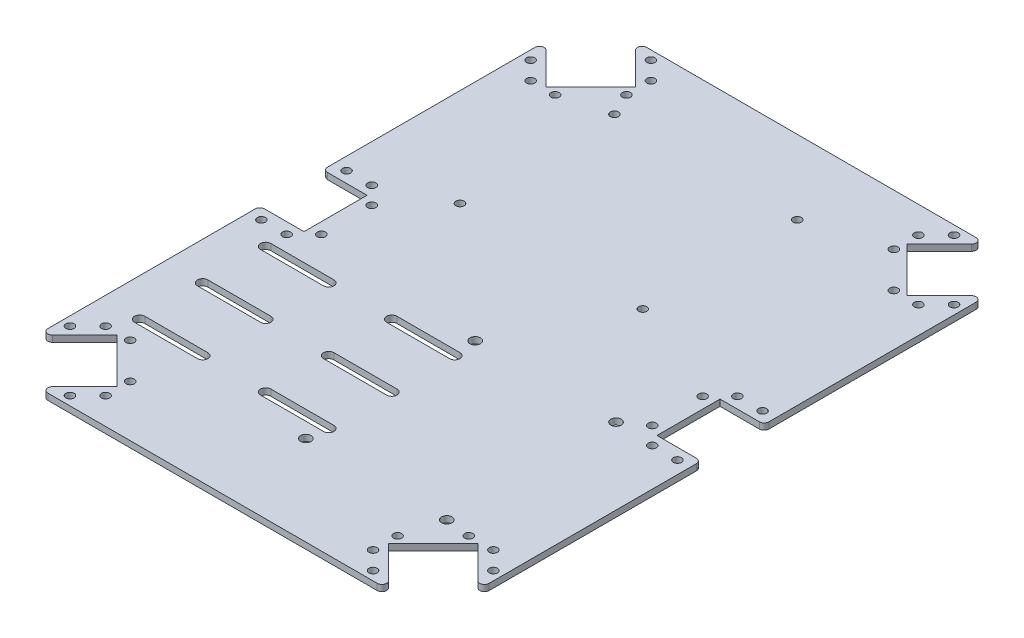
SolidWorks part; units mm, degrees
ref_plane "Front Plane" through (0, 0, 0) normal (0, 0, 1) x (1, 0, 0)
ref_plane "Top Plane" through (0, 0, 0) normal (0, 1, 0) x (1, 0, 0)
ref_plane "Right Plane" through (0, 0, 0) normal (1, 0, 0) x (0, 0, -1)
sketch "Sketch2" plane through (0, 0, 0) normal (0, 1, 0) x (1, 0, 0)
  line L0 (-70, 0) -> (70, 0) construction
  line L1 (-70, 95) -> (70, 95)
  line L2 (-70, 95) -> (-70, -95)
  line L3 (-70, -95) -> (70, -95)
  line L4 (70, 95) -> (70, -95)
  line L5 (70, 95) -> (0, 25) construction
  line L7 (0, 95) -> (0, -95) construction
  line L8 (42.4228, 78.7365) -> (38.5337, 82.6256) construction
  line L9 (38.5337, 82.6256) -> (42.4228, 86.5147) construction
  line L10 (42.4228, 86.5147) -> (48.0797, 92.1716) construction
  line L11 (48.0797, 92.1716) -> (50.9081, 95) construction
  circle A5 centre (42.4228, 78.7365) radius 1.3
  circle A6 centre (42.4228, 86.5147) radius 1.3
  circle A7 centre (48.0797, 92.1716) radius 1.3
  circle A8 centre (66, 13.5) radius 1.3
  circle A9 centre (58, 13.5) radius 1.3
  circle A10 centre (52.5, 8) radius 1.3
  circle A11 centre (52.5, -8) radius 1.3
  circle A12 centre (58, -13.5) radius 1.3
  circle A13 centre (66, -13.5) radius 1.3
  circle A14 centre (67.1716, 73.0797) radius 1.3
  circle A15 centre (61.5147, 67.4228) radius 1.3
  circle A16 centre (53.7365, 67.4228) radius 1.3
  circle A17 centre (67.1716, -73.0797) radius 1.3
  circle A18 centre (61.5147, -67.4228) radius 1.3
  circle A19 centre (53.7365, -67.4228) radius 1.3
  circle A20 centre (48.0797, -92.1716) radius 1.3
  circle A21 centre (42.4228, -86.5147) radius 1.3
  circle A22 centre (42.4228, -78.7365) radius 1.3
  circle A23 centre (-48.0797, 92.1716) radius 1.3
  circle A24 centre (-42.4228, 86.5147) radius 1.3
  circle A25 centre (-42.4228, 78.7365) radius 1.3
  circle A26 centre (-67.1716, 73.0797) radius 1.3
  circle A27 centre (-61.5147, 67.4228) radius 1.3
  circle A28 centre (-53.7365, 67.4228) radius 1.3
  circle A29 centre (-67.1716, -73.0797) radius 1.3
  circle A30 centre (-61.5147, -67.4228) radius 1.3
  circle A31 centre (-53.7365, -67.4228) radius 1.3
  circle A32 centre (-42.4228, -78.7365) radius 1.3
  circle A33 centre (-42.4228, -86.5147) radius 1.3
  circle A34 centre (-48.0797, -92.1716) radius 1.3
  circle A35 centre (-52.5, -8) radius 1.3
  circle A36 centre (-58, -13.5) radius 1.3
  circle A37 centre (-66, -13.5) radius 1.3
  circle A38 centre (-66, 13.5) radius 1.3
  circle A39 centre (-58, 13.5) radius 1.3
  circle A40 centre (-52.5, 8) radius 1.3
  point P0 (0, 0)
  point P27 (0, 0)
  dimension "D6" = 5.5
  dimension "D10" = 8
  dimension "D11" = 5.5
  dimension "D2" = 2.6
  dimension "D3" = 8
  dimension "D4" = 4
  dimension "D5" = 5.5
  dimension "D7" = 45
  dimension "D8" = 140
  dimension "D9" = 190
  dimension "D12" = 5.5
  dimension "D13" = 8
  dimension "D14" = 4
  dimension "D15" = 8
extrude "Boss-Extrude1" add sketch "Sketch2" along normal blind 2
sketch "Sketch3" plane through (0, 2, 0) normal (0, 1, 0) x (1, 0, 0)
  line L0 (0, -95) -> (0, 95) construction
  line L1 (-70, -95) -> (70, -95) construction
  line L2 (70, 95) -> (-70, 95) construction
  line L3 (-70, 0) -> (70, 0) construction
  line L4 (-70, 95) -> (-70, -95) construction
  line L5 (70, -95) -> (70, 95) construction
  line L6 (70, 95) -> (0, 25) construction
  line L7 (70, -10) -> (56, -10)
  line L8 (70, -10) -> (70, 10)
  line L9 (70, 10) -> (56, 10)
  line L10 (56, -10) -> (56, 10)
  line L11 (55.8579, 95) -> (43.1299, 82.2721)
  line L12 (43.1299, 82.2721) -> (57.2721, 68.1299)
  line L13 (57.2721, 68.1299) -> (70, 80.8579)
  line L14 (70, 80.8579) -> (70, 95)
  line L15 (70, 95) -> (55.8579, 95)
  line L16 (70, -80.8579) -> (70, -95)
  line L17 (57.2721, -68.1299) -> (70, -80.8579)
  line L18 (43.1299, -82.2721) -> (57.2721, -68.1299)
  line L19 (55.8579, -95) -> (43.1299, -82.2721)
  line L20 (70, -95) -> (55.8579, -95)
  line L21 (-70, 80.8579) -> (-70, 95)
  line L22 (-57.2721, 68.1299) -> (-70, 80.8579)
  line L23 (-43.1299, 82.2721) -> (-57.2721, 68.1299)
  line L24 (-55.8579, 95) -> (-43.1299, 82.2721)
  line L25 (-70, 95) -> (-55.8579, 95)
  line L26 (-70, 10) -> (-56, 10)
  line L27 (-56, -10) -> (-56, 10)
  line L28 (-70, -10) -> (-56, -10)
  line L29 (-70, -10) -> (-70, 10)
  line L30 (-57.2721, -68.1299) -> (-70, -80.8579)
  line L31 (-43.1299, -82.2721) -> (-57.2721, -68.1299)
  line L32 (-55.8579, -95) -> (-43.1299, -82.2721)
  line L33 (-70, -95) -> (-55.8579, -95)
  line L34 (-70, -80.8579) -> (-70, -95)
  dimension "D1" = 10
  dimension "D2" = 20
  dimension "D3" = 14
  dimension "D4" = 45
  dimension "D5" = 18
  dimension "D6" = 20
  dimension "D7" = 10
extrude "Cut-Extrude1" cut sketch "Sketch3" against normal up to surface (2 mm away) up to face at (0, 0, 0)
fillet "Fillet1" radius 1.5 12 edges at (-70, 1, 10) (-70, 1, -10) (-70, 1, 80.8579) (-55.8579, 1, 95) (55.8579, 1, 95) (70, 1, 80.8579) (70, 1, 10) (70, 1, -10) (70, 1, -80.8579) (55.8579, 1, -95) (-70, 1, -80.8579) (-55.8579, 1, -95)
sketch "Sketch4" plane through (0, 2, 0) normal (0, 1, 0) x (1, 0, 0)
  line L1 (-39, 71.5) -> (19, 71.5) construction
  line L2 (-39, 71.5) -> (-39, 22.5) construction
  line L3 (-39, 22.5) -> (19, 22.5) construction
  line L4 (19, 71.5) -> (19, 22.5) construction
  line L5 (-42.5, 75) -> (42.5, 75) construction
  line L6 (-42.5, 75) -> (-42.5, 19) construction
  line L7 (-42.5, 19) -> (42.5, 19) construction
  line L8 (42.5, 75) -> (42.5, 19) construction
  line L9 (52.2365, 95) -> (-52.2365, 95) construction
  line L10 (-70, 77.2365) -> (-70, 11.5) construction
  circle A0 centre (-39, 71.5) radius 1.3
  circle A1 centre (19, 71.5) radius 1.3
  circle A2 centre (19, 22.5) radius 1.3
  circle A3 centre (-39, 22.5) radius 1.3
  dimension "D1" = 2.6
  dimension "D2" = 58
  dimension "D3" = 85
  dimension "D4" = 56
  dimension "D5" = 49
  dimension "D6" = 3.5
  dimension "D7" = 3.5
  dimension "D8" = 3.5
  dimension "D9" = 20
  dimension "D10" = 27.5
extrude "Cut-Extrude2" cut sketch "Sketch4" against normal up to surface (2 mm away) up to face at (0, 0, 0)
sketch "Sketch5" plane through (0, 2, 0) normal (0, 1, 0) x (1, 0, 0)
  line L4 (-58, -58.4946) -> (-38, -58.4946)
  line L12 (-58, -61.7946) -> (-38, -61.7946)
  line L13 (-58, -38.4946) -> (-38, -38.4946)
  line L14 (-58, -41.7946) -> (-38, -41.7946)
  line L15 (-58, -18.4946) -> (-38, -18.4946)
  line L16 (-58, -21.7946) -> (-38, -21.7946)
  line L17 (-70, -11.5) -> (-70, -77.2365) construction
  line L18 (-28, -95) -> (-28, 95) construction
  line L19 (-52.2365, -95) -> (52.2365, -95) construction
  line L20 (52.2365, 95) -> (-52.2365, 95) construction
  line L22 (2, -21.7946) -> (-18, -21.7946)
  line L23 (2, -18.4946) -> (-18, -18.4946)
  line L24 (2, -41.7946) -> (-18, -41.7946)
  line L25 (2, -38.4946) -> (-18, -38.4946)
  line L26 (2, -61.7946) -> (-18, -61.7946)
  line L27 (2, -58.4946) -> (-18, -58.4946)
  arc A0 (-58, -58.4946) -> (-58, -61.7946) centre (-58, -60.1446) ccw
  arc A1 (-38, -61.7946) -> (-38, -58.4946) centre (-38, -60.1446) ccw
  arc A12 (-58, -38.4946) -> (-58, -41.7946) centre (-58, -40.1446) ccw
  arc A13 (-38, -41.7946) -> (-38, -38.4946) centre (-38, -40.1446) ccw
  arc A14 (-58, -18.4946) -> (-58, -21.7946) centre (-58, -20.1446) ccw
  arc A15 (-38, -21.7946) -> (-38, -18.4946) centre (-38, -20.1446) ccw
  arc A16 (-18, -21.7946) -> (-18, -18.4946) centre (-18, -20.1446) cw
  arc A17 (2, -18.4946) -> (2, -21.7946) centre (2, -20.1446) cw
  arc A18 (-18, -41.7946) -> (-18, -38.4946) centre (-18, -40.1446) cw
  arc A19 (2, -38.4946) -> (2, -41.7946) centre (2, -40.1446) cw
  arc A20 (-18, -61.7946) -> (-18, -58.4946) centre (-18, -60.1446) cw
  arc A21 (2, -58.4946) -> (2, -61.7946) centre (2, -60.1446) cw
  dimension "D1" = 3.3
  dimension "D2" = 20
  dimension "D4" = 12
  dimension "D5" = 10
  dimension "D3" = 3
extrude "Cut-Extrude3" cut sketch "Sketch5" against normal up to surface (2 mm away) contours A1 | A1 L4 A0 | A1 | A0 | L13 A13 L14 A12 | L15 A15 L16 A14 | A16 L23 A17 L22 | A18 L25 A19 L24 | A20 L27 A21 L26 region at (-48, 2, 60.1446) up to face at (-39, 0, -21.2)
sketch "Sketch6" plane through (0, 2, 0) normal (0, 1, 0) x (1, 0, 0)
  line L1 (-0.5119, -68.1784) -> (-0.5119, -11.1784) construction
  line L2 (-0.5119, -68.1784) -> (47.4881, -68.1784) construction
  line L3 (47.4881, -68.1784) -> (47.4881, -11.1784) construction
  line L4 (-0.5119, -11.1784) -> (47.4881, -11.1784) construction
  line L5 (1.1381, -66.5284) -> (1.1381, -12.8284) construction
  line L6 (1.1381, -66.5284) -> (45.8381, -66.5284) construction
  line L7 (45.8381, -66.5284) -> (45.8381, -12.8284) construction
  line L8 (1.1381, -12.8284) -> (45.8381, -12.8284) construction
  circle A0 centre (1.1381, -66.5284) radius 1.65
  circle A1 centre (1.1381, -12.8284) radius 1.65
  circle A2 centre (45.8381, -12.8284) radius 1.65
  circle A3 centre (45.8381, -66.5284) radius 1.65
  dimension "D3" = 3.3
  dimension "D1" = 48
  dimension "D2" = 57
  dimension "D4" = 1.65
  dimension "D5" = 1.65
  dimension "D6" = 1.65
  dimension "D7" = 1.65
extrude "Cut-Extrude4" cut sketch "Sketch6" against normal up to surface (2 mm away) up to face at (-8, 0, 40.1446)
